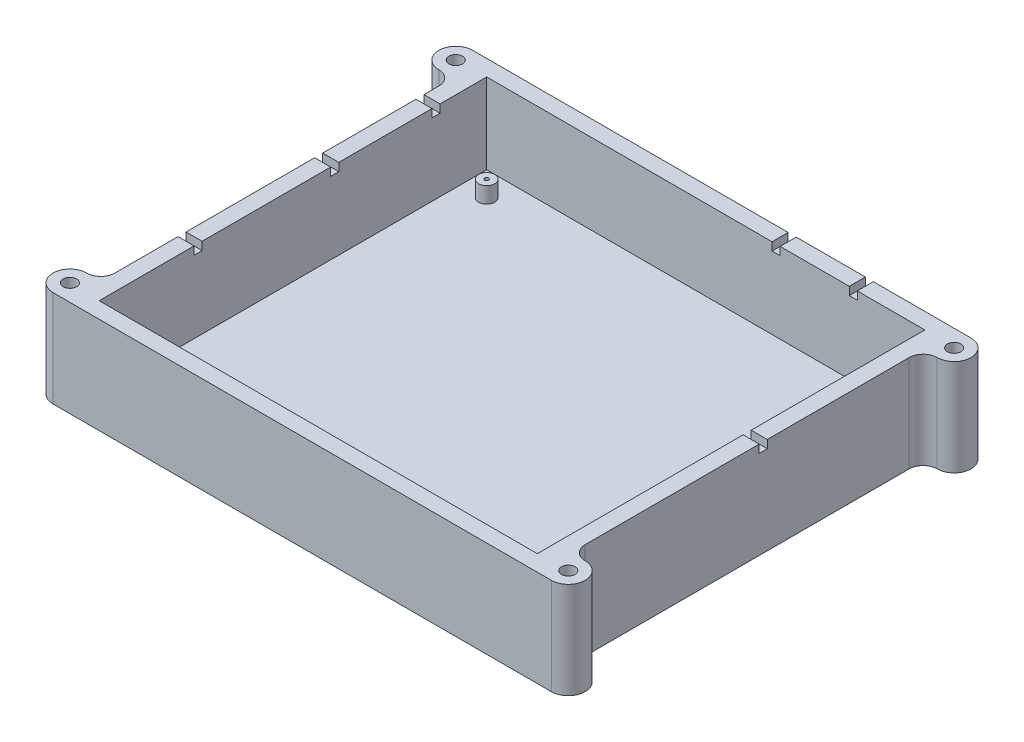
SolidWorks part; units mm, degrees
ref_plane "Front Plane" through (0, 0, 0) normal (0, 0, 1) x (1, 0, 0)
ref_plane "Top Plane" through (0, 0, 0) normal (0, 1, 0) x (1, 0, 0)
ref_plane "Right Plane" through (0, 0, 0) normal (1, 0, 0) x (0, 0, -1)
sketch "Sketch1" plane through (0, 0, 0) normal (0, 1, 0) x (1, 0, 0)
  line L0 (0, 0) -> (-5.55, 0)
  line L1 (0, 0) -> (185.75, 0)
  line L2 (0, 0) -> (0, 165.75)
  line L3 (0, 165.75) -> (185.75, 165.75)
  line L4 (185.75, 0) -> (185.75, 165.75)
  line L5 (6.35, 159.4) -> (179.4, 159.4)
  line L6 (6.35, 159.4) -> (6.35, 6.35)
  line L7 (6.35, 6.35) -> (179.4, 6.35)
  line L8 (179.4, 159.4) -> (179.4, 6.35)
  line L9 (0, 18.9) -> (0, 0)
  line L10 (6.35, 82.875) -> (11.0558, 82.875) construction
  line L11 (92.875, 159.4) -> (92.875, 24.0832) construction
  line L12 (0, 165.75) -> (-5.55, 165.75)
  line L13 (0, 146.85) -> (0, 165.75)
  line L14 (185.75, 18.9) -> (185.75, 0)
  line L15 (185.75, 0) -> (191.3, 0)
  line L16 (185.75, 146.85) -> (185.75, 165.75)
  line L17 (185.75, 165.75) -> (191.3, 165.75)
  line L19 (0, 140.985) -> (6.35, 140.985)
  line L20 (0, 140.985) -> (0, 137.81)
  line L21 (0, 137.81) -> (6.35, 137.81)
  line L22 (6.35, 140.985) -> (6.35, 137.81)
  line L23 (0, 100.98) -> (6.35, 100.98)
  line L24 (0, 100.98) -> (0, 97.805)
  line L25 (0, 97.805) -> (6.35, 97.805)
  line L26 (6.35, 100.98) -> (6.35, 97.805)
  line L27 (0, 47.005) -> (6.35, 47.005)
  line L28 (0, 47.005) -> (0, 43.83)
  line L29 (0, 43.83) -> (6.35, 43.83)
  line L30 (6.35, 47.005) -> (6.35, 43.83)
  line L31 (119.075, 165.75) -> (122.25, 165.75)
  line L32 (119.075, 165.75) -> (119.075, 159.4)
  line L33 (119.075, 159.4) -> (122.25, 159.4)
  line L34 (122.25, 165.75) -> (122.25, 159.4)
  line L35 (149.555, 165.75) -> (152.73, 165.75)
  line L36 (149.555, 165.75) -> (149.555, 159.4)
  line L37 (149.555, 159.4) -> (152.73, 159.4)
  line L38 (152.73, 165.75) -> (152.73, 159.4)
  line L39 (179.4, 90.82) -> (185.75, 90.82)
  line L40 (179.4, 90.82) -> (179.4, 87.645)
  line L41 (179.4, 87.645) -> (185.75, 87.645)
  line L42 (185.75, 90.82) -> (185.75, 87.645)
  circle A0 centre (15.875, 15.875) radius 3.175
  arc A2 (-5.55, 0) -> (-5.55, 13.35) centre (-5.55, 6.675) cw
  arc A3 (-5.55, 13.35) -> (0, 18.9) centre (-5.55, 18.9) ccw
  arc A4 (-5.55, 152.4) -> (0, 146.85) centre (-5.55, 146.85) cw
  arc A5 (-5.55, 165.75) -> (-5.55, 152.4) centre (-5.55, 159.075) ccw
  circle A6 centre (-5.55, 6.675) radius 2.667
  circle A7 centre (-5.55, 159.075) radius 2.667
  circle A8 centre (191.3, 6.675) radius 2.667
  circle A9 centre (191.3, 159.075) radius 2.667
  arc A10 (191.3, 13.35) -> (185.75, 18.9) centre (191.3, 18.9) cw
  arc A11 (191.3, 0) -> (191.3, 13.35) centre (191.3, 6.675) ccw
  arc A12 (191.3, 152.4) -> (185.75, 146.85) centre (191.3, 146.85) ccw
  arc A13 (191.3, 165.75) -> (191.3, 152.4) centre (191.3, 159.075) cw
  circle A14 centre (169.875, 15.875) radius 3.175
  circle A15 centre (169.875, 149.875) radius 3.175
  circle A16 centre (15.875, 149.875) radius 3.175
  point P9 (92.875, 159.4)
  point P10 (6.35, 82.875)
  point P11 (92.875, 82.875)
  point P72 (3.175, 100.98)
  dimension "D7" = 6.35
  dimension "D12" = 5.334
  dimension "D2" = 6.35
  dimension "D3" = 6.35
  dimension "D4" = 6.35
  dimension "D5" = 6.35
  dimension "D6" = 9.525
  dimension "D8" = 67
  dimension "D9" = 77
  dimension "D10" = 9.525
  dimension "D11" = 3.175
  dimension "D13" = 196.85
  dimension "D14" = 152.4
  dimension "D15" = 3.175
  dimension "D16" = 3.175
  dimension "D17" = 24.765
  dimension "D18" = 64.77
  dimension "D19" = 118.745
  dimension "D20" = 3.175
  dimension "D21" = 3.175
  dimension "D22" = 3.175
  dimension "D23" = 63.5
  dimension "D24" = 33.02
  dimension "D25" = 74.93
extrude "Boss-Extrude1" add sketch "Sketch1" along normal blind 6.35 contours L8 L5 L6 L7 A14 A0 | A14 | L1 L4 L3 L2 L5 L8 L7 L6 | A16 | A15 | A14 | A0 | L2 L29 L6 L27 | L2 L27 L6 L25 | L2 L25 L6 L23 | L2 L23 L6 L21 | L2 L21 L6 L19 | L32 L3 L2 L19 L6 L5 | L34 L3 L32 L5 | L36 L3 L34 L5 | L38 L3 L36 L5 | L8 L39 L4 L3 L38 L5 | L8 L41 L4 L39 | L0 A2 A3 L9 | L12 A5 A4 L13 region at (2.0539, 0, -9.45) region at (3.175, 0, -45.4175) region at (182.575, 0, -89.2325) region at (3.175, 0, -72.405) region at (92.875, 0, -82.875) region at (182.575, 0, -91.6388) region at (3.175, 0, -99.3925) region at (3.175, 0, -119.395) region at (3.175, 0, -139.3975) region at (151.1425, 0, -162.575) region at (51.9885, 0, -160.9165) region at (135.9025, 0, -162.575) region at (120.6625, 0, -162.575) region at (15.875, 0, -15.875) region at (169.875, 0, -15.875) region at (169.875, 0, -149.875) region at (15.875, 0, -149.875)
extrude "Boss-Extrude2" add sketch "Sketch1<3>" along normal blind 6.35 from surface contours A0 | A16 | A15 | A14 region at (15.875, 0, -15.875) region at (169.875, 0, -15.875) region at (169.875, 0, -149.875) region at (15.875, 0, -149.875) starting at face at (42.2811, 6.35, -82.875)
sketch "Sketch1<3>" plane through (0, 0, 0) normal (0, 1, 0) x (1, 0, 0) same geometry as "Sketch1"
extrude "Boss-Extrude3" add sketch "Sketch1<4>" along normal offset from surface (38.1 mm away) 25.4 contours L1 L4 L3 L2 L5 L8 L7 L6 | L2 L27 L6 L25 | L2 L25 L6 L23 | L2 L23 L6 L21 | L2 L21 L6 L19 | L32 L3 L2 L19 L6 L5 | L36 L3 L34 L5 | L8 L39 L4 L3 L38 L5 | L8 L41 L4 L39 | L27 L30 L29 L28 | L34 L33 L32 L31 | L36 L37 L38 L35 region at (2.0539, 0, -9.45) region at (182.575, 0, -89.2325) region at (3.175, 0, -72.405) region at (182.575, 0, -91.6388) region at (3.175, 0, -99.3925) region at (3.175, 0, -119.395) region at (3.175, 0, -139.3975) region at (51.9885, 0, -160.9165) region at (135.9025, 0, -162.575) up to face at (15.875, 12.7, -12.7) offset beyond the face yes
sketch "Sketch1<4>" plane through (0, 0, 0) normal (0, 1, 0) x (1, 0, 0) same geometry as "Sketch1"
extrude "Boss-Extrude4" add sketch "Sketch1<5>" along normal up to surface (38.1 mm away) contours A3 A2 L0 L2 A6 | L12 A5 A4 L2 A7 | L15 A11 A10 L4 A8 | A13 L17 L4 A12 A9 region at (-2.775, 0, -0.2251) region at (185.9751, 0, -9.45) region at (185.9751, 0, -156.3) region at (-1.4664, 0, -150.9336) up to face at (92.875, 38.1, -82.875)
sketch "Sketch1<5>" plane through (0, 0, 0) normal (0, 1, 0) x (1, 0, 0) same geometry as "Sketch1"
hole_wizard "M2x0.4 Tapped Hole1" positions "Sketch2" profile "Sketch4" tap size "M2x0.4" standard "ANSI Metric"
sketch "Sketch2" plane through (0, 12.7, 0) normal (0, 1, 0) x (1, 0, 0)
  point P0 (15.875, 15.875)
  point P3 (169.875, 15.875)
  point P6 (15.875, 149.875)
  point P9 (169.875, 149.875)
sketch "Sketch4" plane through (15.875, 12.7, -15.875) normal (1, 0, 0) x (0, 0, 1)
  line L0 (0, 0) -> (0, 5.6801)
  line L1 (0, 5.6801) -> (0.8, 5.1994)
  line L2 (0.8, 5.1994) -> (0.8, 0)
  line L5 (0.8, 0) -> (0, 0)
  line L10 (0, 5.6801) -> (-0.8, 5.1994) construction
  line L11 (0, -6.35) -> (0, 107.95) construction
  dimension "Tap Drill Dia." = 1.6
  dimension "Tap Drill Depth" = 5.1994
  dimension "Drill Angle" = 118
cosmetic thread "Hole Thread1" parameters "D1"=4.0005, "D2"=2
cosmetic thread "Hole Thread2" parameters "D1"=4.0005, "D2"=2
cosmetic thread "Hole Thread3" parameters "D1"=4.0005, "D2"=2
cosmetic thread "Hole Thread4" parameters "D1"=4.0005, "D2"=2
extrude "Cut-Extrude1" cut sketch "Sketch1<6>" against normal blind 3.175 from surface contours L2 L29 L6 L27 | L2 L25 L6 L23 | L2 L21 L6 L19 | L34 L3 L32 L5 | L38 L3 L36 L5 | L8 L41 L4 L39 region at (3.175, 0, -45.4175) region at (182.575, 0, -89.2325) region at (3.175, 0, -99.3925) region at (3.175, 0, -139.3975) region at (151.1425, 0, -162.575) region at (120.6625, 0, -162.575) starting at face at (92.875, 38.1, -82.875)
sketch "Sketch1<6>" plane through (0, 0, 0) normal (0, 1, 0) x (1, 0, 0) same geometry as "Sketch1"
